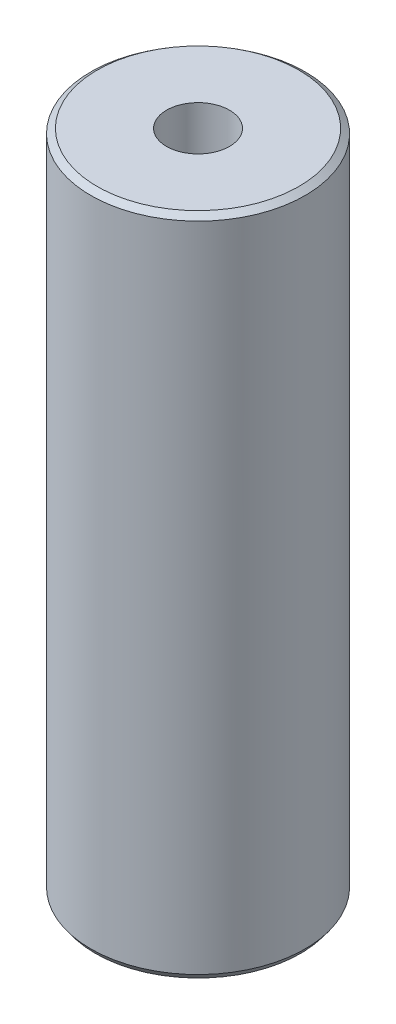
SolidWorks part; units mm, degrees
ref_plane "Front Plane" through (0, 0, 0) normal (0, 0, 1) x (1, 0, 0)
ref_plane "Top Plane" through (0, 0, 0) normal (0, 1, 0) x (1, 0, 0)
ref_plane "Right Plane" through (0, 0, 0) normal (1, 0, 0) x (0, 0, -1)
sketch "Sketch1" plane through (0, 0, 0) normal (0, 1, 0) x (1, 0, 0)
  circle A0 centre (0, 0) radius 55
  dimension "SHAFT_OD" = 110
extrude "Boss-Extrude1" add sketch "Sketch1" along normal blind 340.4497
sketch "Sketch2" plane through (0, 0, 0) normal (0, 1, 0) x (1, 0, 0)
  circle A0 centre (0, 0) radius 16.1535
  dimension "BORE_D" = 32.3069
extrude "Cut-Extrude1" cut sketch "Sketch2" along normal through all
chamfer "Chamfer1" distance 2.382 angle 53.667 2 edges at (0, 340.4497, 55) (0, 0, 55) first distance on face at (0, 340.4497, 55) first distance on face at (0, 0, 16.1535)
